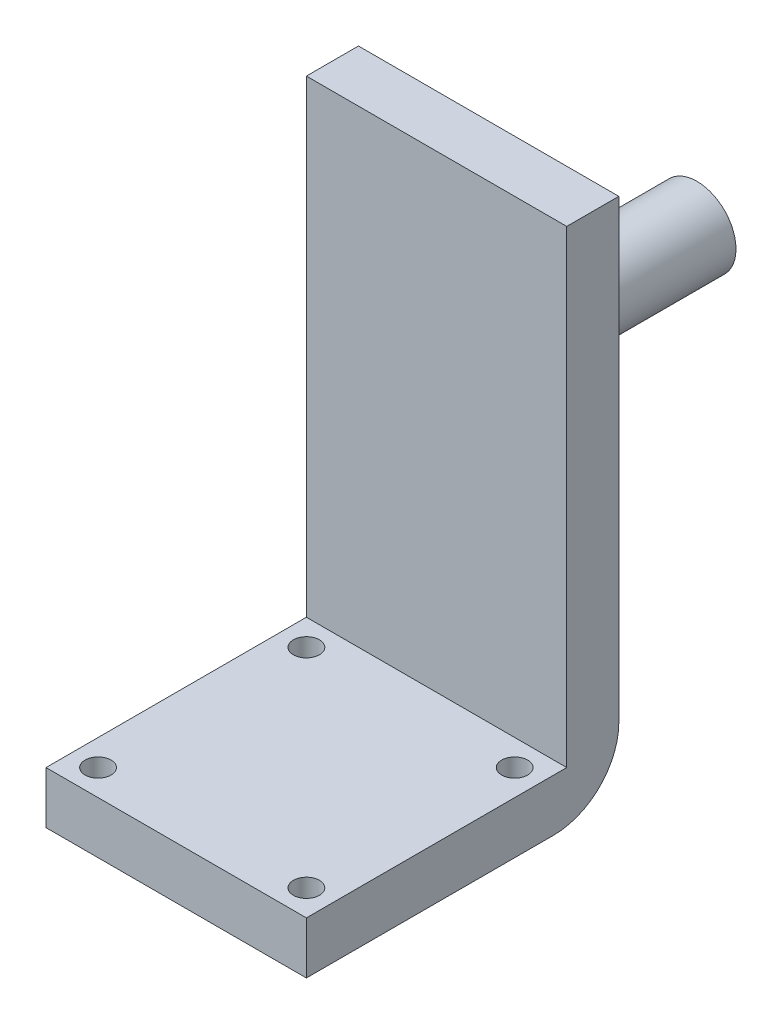
SolidWorks part; units mm, degrees
ref_plane "Front Plane" through (0, 0, 0) normal (0, 0, 1) x (1, 0, 0)
ref_plane "Top Plane" through (0, 0, 0) normal (0, 1, 0) x (1, 0, 0)
ref_plane "Right Plane" through (0, 0, 0) normal (1, 0, 0) x (0, 0, -1)
sketch "Sketch1" plane through (0, 0, 0) normal (0, 1, 0) x (1, 0, 0)
  line L1 (-10, -10) -> (10, -10)
  line L2 (-10, -10) -> (-10, 10)
  line L3 (-10, 10) -> (10, 10)
  line L4 (10, -10) -> (10, 10)
  circle A0 centre (-8, 8) radius 1
  circle A1 centre (-8, -8) radius 1
  circle A2 centre (8, -8) radius 1
  circle A3 centre (8, 8) radius 1
  point P0 (0, 0)
  point P16 (-8.1456, -10)
  point P17 (8.2338, -10)
  point P18 (8.7845, -5.4715)
  dimension "D3" = 2
  dimension "D1" = 20
  dimension "D2" = 20
  dimension "D4" = 2
  dimension "D5" = 2
  dimension "D6" = 2
  dimension "D7" = 2
  dimension "D8" = 2
  dimension "D9" = 2
  dimension "D10" = 2
  dimension "D11" = 2
extrude "Boss-Extrude1" add sketch "Sketch1" along normal blind 4
sketch "Sketch2" plane through (0, 0, -10) normal (0, 0, -1) x (-1, 0, 0)
  line L0 (-10, 4) -> (-10, 0) construction
  line L1 (-10, 0) -> (10, 0)
  line L2 (-10, 0) -> (-10, 40)
  line L3 (-10, 40) -> (10, 40)
  line L4 (10, 0) -> (10, 40)
  line L5 (-10, 0) -> (10, 0) construction
  line L6 (10, 4) -> (10, 0) construction
  circle A0 centre (0, 25) radius 3
  dimension "D3" = 6
  dimension "D1" = 40
  dimension "D2" = 25
extrude "Boss-Extrude2" add sketch "Sketch2" along normal blind 4
fillet "Fillet1" radius 5 1 edges at (0, 0, -14)
sketch "Sketch3" plane through (0, 0, -10) normal (0, 0, 1) x (1, 0, 0)
  circle A0 centre (0, 25) radius 3 construction
  circle A1 centre (0, 25) radius 3
extrude "Boss-Extrude3" add sketch "Sketch3" against normal blind 20
